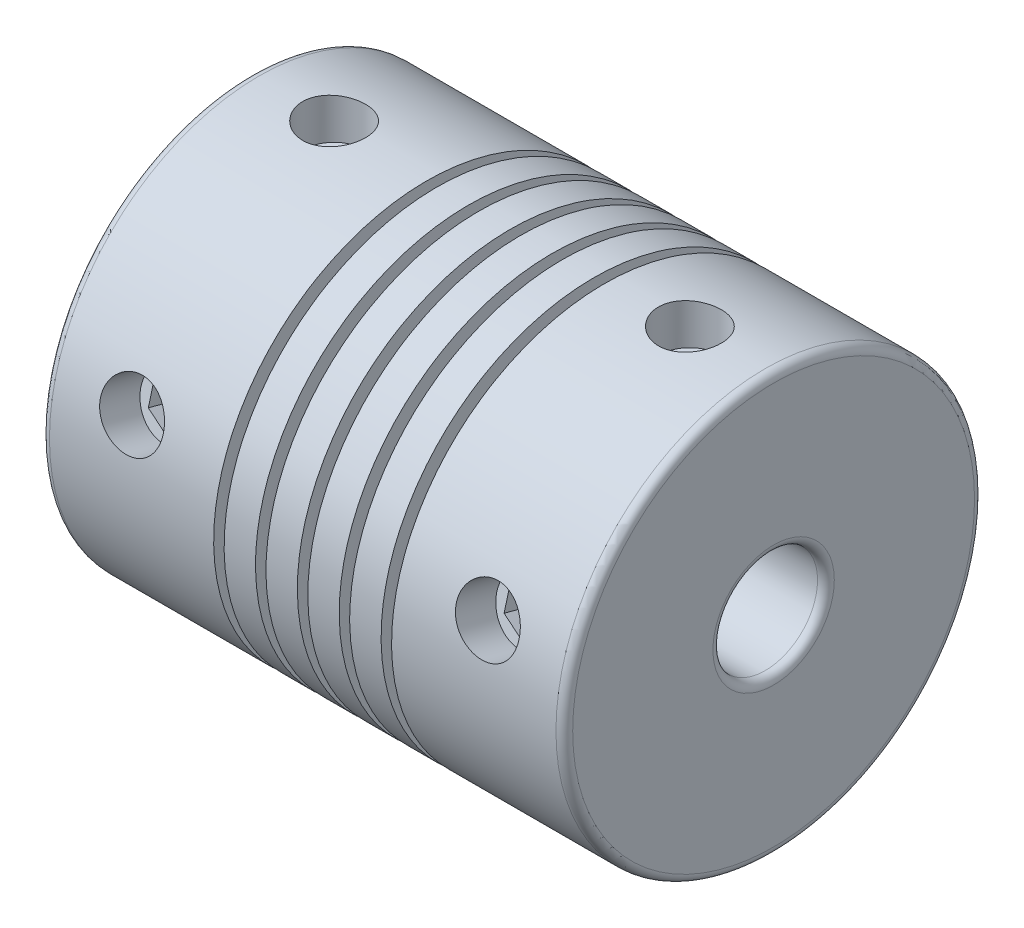
SolidWorks part; units mm, degrees
material "1060 Alloy"
ref_plane "Front Plane" through (0, 0, 0) normal (0, 0, 1) x (1, 0, 0)
ref_plane "Top Plane" through (0, 0, 0) normal (0, 1, 0) x (1, 0, 0)
ref_plane "Right Plane" through (0, 0, 0) normal (1, 0, 0) x (0, 0, -1)
sketch "Sketch1" plane through (0, 0, 0) normal (1, 0, 0) x (0, 0, -1)
  circle A0 centre (0, 0) radius 10
  circle A1 centre (0, 0) radius 2.5
  dimension "D1" = 20
  dimension "D2" = 5
extrude "Boss-Extrude1" add sketch "Sketch1" along normal blind 17.5 and the other way blind 7.5
sketch "Sketch2" plane through (0, 0, 0) normal (0, 1, 0) x (1, 0, 0)
  line L0 (5, 10) -> (5, -4.0374) construction
  line L1 (17.5, 10) -> (-7.5, 10) construction
  circle A0 centre (13.5, 0) radius 1.5
  circle A1 centre (-3.5, 0) radius 1.5
  dimension "D1" = 3
  dimension "D2" = 17
extrude "Cut-Extrude1" cut sketch "Sketch2" along normal up to next from offset 8
sketch "Sketch4" plane through (0, 8, 0) normal (0, 1, 0) x (1, 0, 0)
  line L0 (17.5, -10) -> (17.5, 10) construction
  line L1 (14.5, 0.5774) -> (13.5, 1.1547)
  line L2 (13.5, 1.1547) -> (12.5, 0.5774)
  line L3 (12.5, 0.5774) -> (12.5, -0.5774)
  line L4 (12.5, -0.5774) -> (13.5, -1.1547)
  line L5 (13.5, -1.1547) -> (14.5, -0.5774)
  line L6 (14.5, -0.5774) -> (14.5, 0.5774)
  line L7 (5, 10) -> (5, -10) construction
  line L8 (17.5, 10) -> (-7.5, 10) construction
  line L9 (-7.5, -10) -> (17.5, -10) construction
  line L10 (-4.5, -0.5774) -> (-4.5, 0.5774)
  line L11 (-3.5, -1.1547) -> (-4.5, -0.5774)
  line L12 (-2.5, -0.5774) -> (-3.5, -1.1547)
  line L13 (-2.5, 0.5774) -> (-2.5, -0.5774)
  line L14 (-3.5, 1.1547) -> (-2.5, 0.5774)
  line L15 (-4.5, 0.5774) -> (-3.5, 1.1547)
  circle A0 centre (13.5, 0) radius 1 construction
  circle A1 centre (-3.5, 0) radius 1 construction
  dimension "D1" = 2
extrude "Cut-Extrude2" cut sketch "Sketch4" against normal blind 1
pattern_circular "CirPattern1" count 2 over 75 about axis through (-7.5, 0, 0) along (1, 0, 0) of "Cut-Extrude1", "Cut-Extrude2"
sketch "Sketch5" plane through (0, 0, 0) normal (1, 0, 0) x (0, 0, -1)
  circle A0 centre (0, 0) radius 10 construction
  circle A1 centre (0, 0) radius 10
curve "Helix/Spiral1" pitch 2 height 10 radius 10 left hand yes centre (0, 0, 0) axis (1, 0, 0) start towards (0, 0, -1)
sketch "Sketch7" plane through (0, 0, 0) normal (0, 1, 0) x (1, 0, 0)
  line L0 (-0.25, 2.5) -> (-7.5, 2.5) construction
  line L1 (-0.25, 10) -> (0.25, 10)
  line L2 (-0.25, 10) -> (-0.25, 2.5)
  line L3 (-0.25, 2.5) -> (0.25, 2.5)
  line L4 (0.25, 10) -> (0.25, 2.5)
  point P4 (0, 10)
  dimension "D1" = 0.5
sweep "Cut-Sweep2" cut profiles "Sketch7" path "Helix/Spiral1"
fillet "Fillet1" radius 0.4 4 edges at (-7.5, 0, -10) (-7.5, 0, -2.5) (17.5, 0, -2.5) (17.5, 0, -10)
